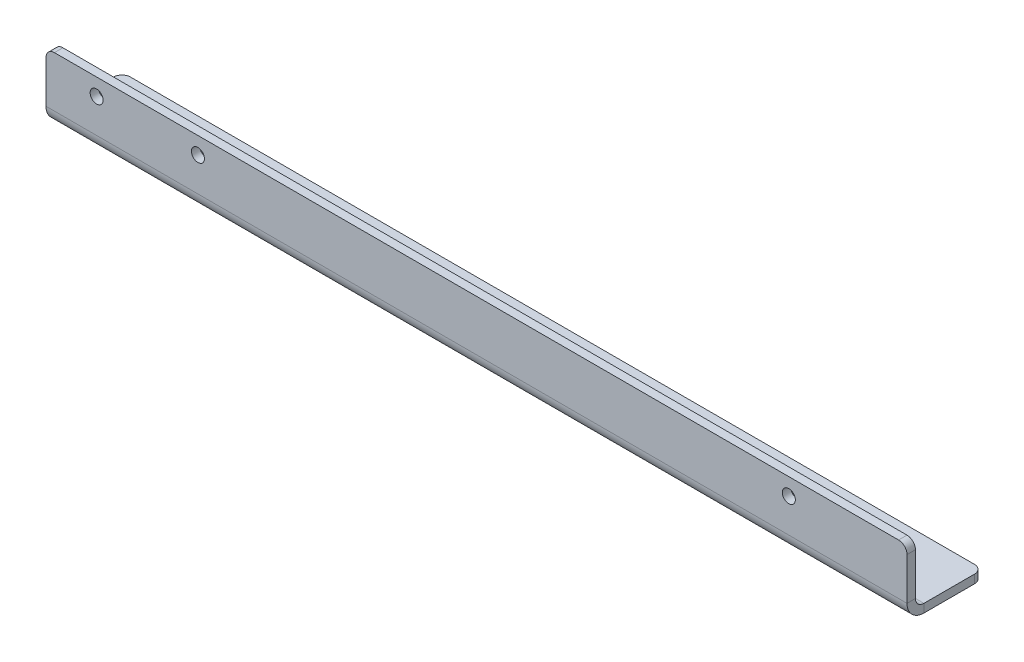
SolidWorks part; units mm, degrees
note: The reader was unsure of these and kept them because the rebuilt part matched: flange length of "Edge-Flange1".
material "5052-H32"
ref_plane "Front Plane" through (0, 0, 0) normal (0, 0, 1) x (1, 0, 0)
ref_plane "Top Plane" through (0, 0, 0) normal (0, 1, 0) x (1, 0, 0)
ref_plane "Right Plane" through (0, 0, 0) normal (1, 0, 0) x (0, 0, -1)
sketch "Sketch3" plane through (0, 0, 0) normal (1, 0, 0) x (0, 0, -1)
  line L0 (0, 0) -> (0, 34.925)
  line L1 (0, 55) -> (0, -55) construction
  line L2 (0, 0) -> (34.925, 0)
  line L3 (55, 0) -> (-55, 0) construction
  dimension "D1" = 34.925
  dimension "D2" = 34.925
sketch "Sketch9" plane through (0, 0, 0) normal (0, 1, 0) x (1, 0, 0)
  line L0 (0, 0) -> (323.85, 0)
  line L1 (-55, 0) -> (55, 0) construction
  line L2 (323.85, 0) -> (323.85, 28.575)
  line L3 (323.85, 28.575) -> (0, 28.575)
  line L4 (0, 28.575) -> (0, 0)
  dimension "D1" = 28.575
  dimension "D2" = 323.85
base flange "Base-Flange2" sketch "Sketch9" thickness 3.175 reverse thickness direction no parameters "D1"=7.62
edge flange "Edge-Flange1" sketch "Sketch14" flange angle 90 flange length 25.4 flange position material inside bend radius 3.175 thickness 3.175 relief rectangular parameters "D6"=10
sketch "Sketch14" plane through (0, 0, 0) normal (0, 0, 1) x (1, 0, 0)
  line L2 (0, 0) -> (0, 22.225)
  line L3 (0, 22.225) -> (323.85, 22.225)
  line L4 (323.85, 22.225) -> (323.85, 0)
  line L11 (0, 0) -> (323.85, 0) construction
  line L12 (0, 0) -> (323.85, 0)
bend "EdgeBend1" bend radius 3.175 bend angle 90 parameters "D5"=1
sketch "Sketch15" plane through (0, 0, 0) normal (0, 1, 0) x (1, 0, 0)
  line L0 (0, 28.575) -> (0, 6.35) construction
  line L1 (323.85, 0) -> (0, 0) construction
  circle A0 centre (19.05, 19.05) radius 2.4511
  circle A1 centre (57.15, 19.05) radius 2.4511
  circle A5 centre (279.4, 19.05) radius 2.4511
  circle A6 centre (501.65, 19.05) radius 2.4511
  dimension "D3" = 4.9022
  dimension "D5" = 4.9022
  dimension "D1" = 19.05
  dimension "D2" = 19.05
  dimension "D4" = 38.1
  dimension "D6" = 19.05
  dimension "D7" = 3
extrude "Cut-Extrude1" cut sketch "Sketch15" against normal blind 3.175 normal cut yes
fillet "Fillet1" radius 3.175 4 edges at (323.85, -1.5875, -28.575) (323.85, 22.225, -1.5875) (0, 22.225, -1.5875) (0, -1.5875, -28.575)
sketch "Sketch16" plane through (0, 0, 0) normal (0, 0, 1) x (1, 0, 0)
  line L0 (323.85, -3.175) -> (0, -3.175) construction
  line L1 (0, 19.05) -> (0, 3.175) construction
  circle A0 centre (19.05, 15.875) radius 2.4511
  circle A1 centre (57.15, 15.875) radius 2.4511
  circle A2 centre (279.4, 15.875) radius 2.4511
  dimension "D3" = 4.9022
  dimension "D4" = 38.1
  dimension "D5" = 4.9022
  dimension "D7" = 19.05
  dimension "D9" = 4.9022
  dimension "D1" = 19.05
  dimension "D2" = 19.05
  dimension "D6" = 19.05
  dimension "D8" = 279.4
extrude "Cut-Extrude2" cut sketch "Sketch16" against normal blind 3.175 normal cut yes
sketch "Bend-Lines1" [suppressed] plane through (0, 0, 0) normal (0, 1, 0) x (1, 0, 0)
sketch "Bounding-Box1" [suppressed] plane through (0, 0, 0) normal (0, 1, 0) x (1, 0, 0)
sheet metal parameters "Sheet-Metal3" thickness 3.175 parameters "D1"=7.62
flat pattern "Flat-Pattern3" [suppressed]
sketch "Bend-Lines3" plane through (0, 0, 0) normal (0, 1, 0) x (1, 0, 0)
sketch3d "Bounding-Box3" [suppressed]
  line L0 (-311.3696, 0, 0) -> (247.4304, 0, 0) construction
  line L1 (-311.3696, 28.575, 0) -> (247.4304, 28.575, 0) construction
  line L2 (-311.3696, 0, 0) -> (-311.3696, 28.575, 0) construction
  line L3 (247.4304, 0, 0) -> (247.4304, 28.575, 0) construction
sheet metal parameters "Sheet-Metal4" thickness 3.175 parameters "D1"=7.62
flat pattern "Flat-Pattern3"
sketch "Bend-Lines3" plane through (0, 0, 0) normal (0, 1, 0) x (1, 0, 0)
  line L0 (-234.7304, 2.6095) -> (308.1946, 2.6095) construction
  line L1 (-234.7304, 2.6095) -> (308.1946, 2.6095) construction
sketch3d "Bounding-Box3" [suppressed]
  line L0 (311.3696, -23.3559, 0) -> (-234.7304, -23.3559, 0) construction
  line L1 (311.3696, 28.575, 0) -> (-234.7304, 28.575, 0) construction
  line L2 (311.3696, -23.3559, 0) -> (311.3696, 28.575, 0) construction
  line L3 (-234.7304, -23.3559, 0) -> (-234.7304, 28.575, 0) construction
bend of the flat pattern "Flatten-<EdgeBend1>1"
sheet metal parameters "Sheet-Metal5" thickness 3.175 parameters "D1"=7.62
flat pattern "Flat-Pattern3"
sketch "Bend-Lines3" plane through (0, 0, 0) normal (0, 1, 0) x (1, 0, 0)
  line L0 (0, 2.6095) -> (323.85, 2.6095) construction
  line L1 (0, 2.6095) -> (323.85, 2.6095) construction
sketch3d "Bounding-Box3" [suppressed]
  line L0 (0, -20.1805, 0) -> (323.85, -20.1809, 0) construction
  line L1 (0.0001, 28.575, 0) -> (323.8501, 28.5746, 0) construction
  line L2 (0, -20.1805, 0) -> (0.0001, 28.575, 0) construction
  line L3 (323.85, -20.1809, 0) -> (323.8501, 28.5746, 0) construction
bend of the flat pattern "Flatten-<EdgeBend1>1"
sheet metal parameters "Sheet-Metal6" thickness 3.175 parameters "D1"=7.62
flat pattern "Flat-Pattern3"
sketch "Bend-Lines3" plane through (0, 0, 0) normal (0, 1, 0) x (1, 0, 0)
  line L0 (0, 2.6095) -> (323.85, 2.6095) construction
  line L1 (0, 2.6095) -> (323.85, 2.6095) construction
sketch3d "Bounding-Box3" [suppressed]
  line L0 (0, -20.1805, 0) -> (323.85, -20.1809, 0) construction
  line L1 (0.0001, 28.575, 0) -> (323.8501, 28.5746, 0) construction
  line L2 (0, -20.1805, 0) -> (0.0001, 28.575, 0) construction
  line L3 (323.85, -20.1809, 0) -> (323.8501, 28.5746, 0) construction
bend of the flat pattern "Flatten-<EdgeBend1>1"
